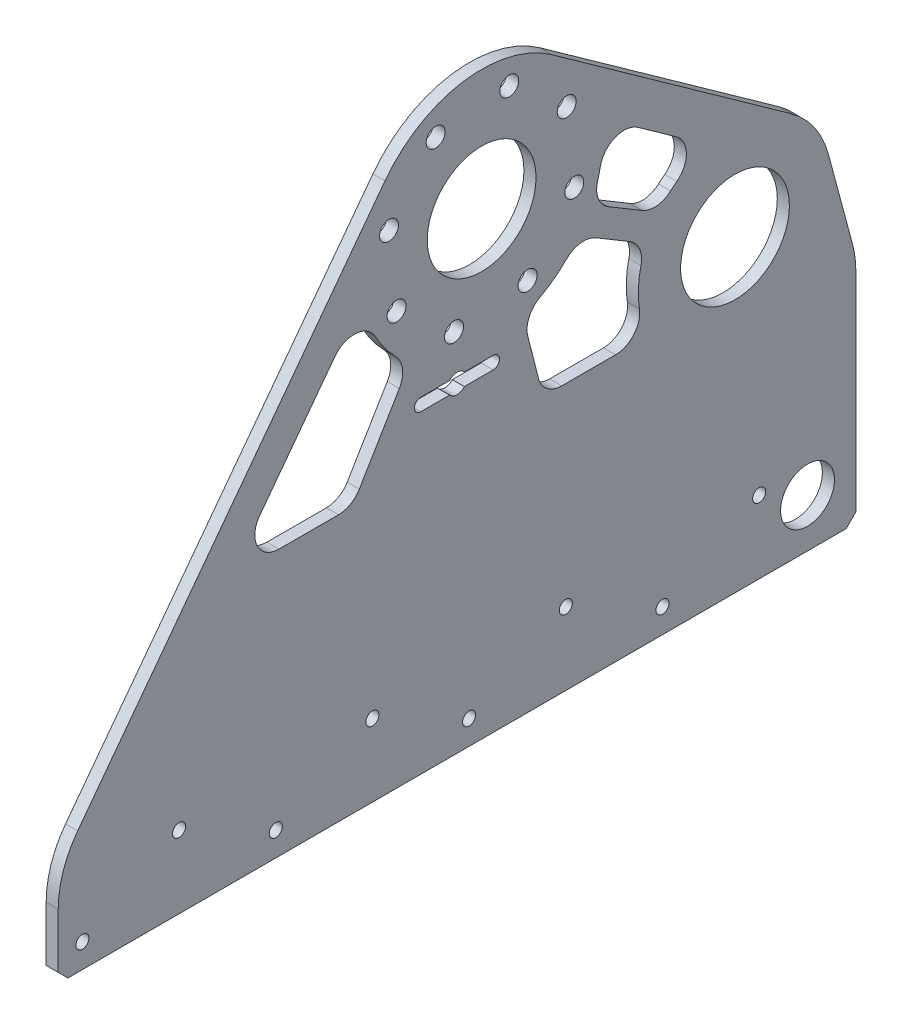
SolidWorks part; units mm, degrees
material "6061-T6 (SS)"
ref_plane "Front Plane" through (0, 0, 0) normal (0, 0, 1) x (1, 0, 0)
ref_plane "Top Plane" through (0, 0, 0) normal (0, 1, 0) x (1, 0, 0)
ref_plane "Right Plane" through (0, 0, 0) normal (1, 0, 0) x (0, 0, -1)
sketch "Sketch1" plane through (0, 0, 0) normal (1, 0, 0) x (0, 0, -1)
  line L0 (0, -25.4) -> (0, 31.864)
  line L13 (-209.55, -25.4) -> (0, -25.4)
  line L14 (-209.55, -25.4) -> (-209.55, -8.4756)
  line L15 (-204.4603, 6.7773) -> (-123.6994, 114.3161)
  line L16 (-209.55, 0) -> (0, 0) construction
  line L17 (-7.2155, 62.1365) -> (-0.8655, 38.438)
  line L18 (-79.8716, 121.0963) -> (-16.9981, 76.2396)
  circle A5 centre (-31.75, 55.5625) radius 14.2875
  circle A6 centre (-98.3115, 95.25) radius 14.2875 construction
  arc A7 (-79.8716, 121.0963) -> (-123.6994, 114.3161) centre (-98.3115, 95.25) ccw
  arc A8 (-16.9981, 76.2396) -> (-7.2155, 62.1365) centre (-31.75, 55.5625) cw
  circle A9 centre (-98.3115, 95.25) radius 14.2875
  arc A10 (-209.55, -8.4756) -> (-204.4603, 6.7773) centre (-184.15, -8.4756) cw
  arc A11 (-0.8655, 38.438) -> (0, 31.864) centre (-25.4, 31.864) cw
  point P4 (0, 0)
  dimension "D4" = 31.75
  dimension "D7" = 25.4
  dimension "D10" = 28.575
  dimension "D3" = 41.275
  dimension "D9" = 25.4
  dimension "D12" = 77.4954
  dimension "D13" = 63.5
  dimension "D14" = 63.5
  dimension "D5" = 25.4
  dimension "D8" = 28.575
  dimension "D2" = 15
  dimension "D6" = 209.55
extrude "Boss-Extrude1" add sketch "Sketch1" along normal blind 3.175
hole_wizard "#10 Clearance Hole1" positions "Sketch2" profile "Sketch3" hole size "#10" standard "ANSI Inch" end condition through all
sketch "Sketch2" plane through (3.175, 0, 0) normal (1, 0, 0) x (0, 0, -1)
  line L0 (-98.3115, 95.25) -> (-31.75, 55.5625) construction
  line L1 (-72.9115, 95.25) -> (-86.2351, 72.9046) construction
  circle A0 centre (-98.3115, 95.25) radius 25.4 construction
  circle A1 centre (-31.75, 55.5625) radius 14.2875 construction
  point P17 (-91.0503, 119.59)
  point P38 (-75.9661, 107.3265)
  point P39 (-73.9716, 87.9887)
  point P40 (-86.2351, 72.9046)
  point P41 (-105.5728, 70.91)
  point P42 (-120.657, 83.1735)
  point P43 (-122.6515, 102.5113)
  point P44 (-110.388, 117.5954)
  dimension "D1" = 50.8
  dimension "D2" = 8
sketch "Sketch3" plane through (3.175, 119.59, 91.0503) normal (0, 1, 0) x (0, 0, -1)
  line L0 (0, 0) -> (0, 3.175)
  line L1 (0, 3.175) -> (2.4892, 3.175)
  line L2 (2.4892, 3.175) -> (2.4892, 0)
  line L5 (2.4892, 0) -> (0, 0)
  line L11 (0, -6.35) -> (0, 107.95) construction
  dimension "Thru Hole Dia." = 4.9784
  dimension "Thru Hole Depth" = 3.175
sketch "Sketch9" plane through (3.175, 0, 0) normal (1, 0, 0) x (0, 0, -1)
  line L0 (0, 0) -> (-208.0942, 0) construction
  line L1 (0, -25.4) -> (0, 31.864) construction
  line L2 (0, -25.4) -> (0, 31.864) construction
  line L3 (-209.55, -25.4) -> (0, -25.4) construction
  line L4 (-164.2565, 44.45) -> (-129.699, 90.4657)
  line L5 (-123.6994, 114.3161) -> (-204.4603, 6.7773) construction
  line L6 (-176.1684, 44.45) -> (-132.2977, 44.45) construction
  line L7 (-164.2565, 44.45) -> (-132.2977, 44.45)
  line L8 (-66.9456, 100.1737) -> (-38.6711, 80.0014)
  line L9 (-16.9981, 76.2396) -> (-79.8716, 121.0963) construction
  line L10 (-69.5519, 81.7985) -> (-51.7692, 71.1955)
  line L11 (-55.0212, 65.7415) -> (-72.8039, 76.3444)
  line L12 (-98.3115, 95.25) -> (-31.75, 55.5625) construction
  line L13 (-98.3115, 95.25) -> (-132.7027, 37.5711) construction
  line L14 (-98.3115, 95.25) -> (-81.8784, 30.2801) construction
  line L15 (-117.2171, 69.7423) -> (-132.2977, 44.45)
  line L16 (-124.9046, 44.45) -> (-111.763, 66.4903) construction
  line L17 (-93.6431, 63.8451) -> (-88.7375, 44.45) construction
  line L18 (-82.1875, 44.45) -> (-87.487, 65.4022)
  line L19 (-82.1875, 44.45) -> (0, 44.45) construction
  line L20 (-82.1875, 44.45) -> (-54.5901, 44.45)
  line L21 (-124.9046, 44.45) -> (-88.7375, 44.45) construction
  line L22 (-124.9046, 44.45) -> (-88.7375, 44.45) construction
  circle A0 centre (-12.7, -12.7) radius 7.0739
  arc A2 (-204.4603, 6.7773) -> (-209.55, -8.4756) centre (-184.15, -8.4756) ccw construction
  arc A3 (-69.5519, 81.7985) -> (-117.2171, 69.7423) centre (-98.3115, 95.25) ccw construction
  arc A4 (-79.8716, 121.0963) -> (-123.6994, 114.3161) centre (-98.3115, 95.25) ccw construction
  arc A5 (-55.0212, 65.7415) -> (-51.7692, 71.1955) centre (-31.75, 55.5625) ccw construction
  arc A6 (-7.2155, 62.1365) -> (-16.9981, 76.2396) centre (-31.75, 55.5625) ccw construction
  arc A7 (-129.699, 90.4657) -> (-117.2171, 69.7423) centre (-98.3115, 95.25) ccw
  arc A8 (-54.5901, 44.45) -> (-55.0212, 65.7415) centre (-31.75, 55.5625) cw
  arc A9 (-51.7692, 71.1955) -> (-38.6711, 80.0014) centre (-31.75, 55.5625) cw
  arc A10 (-69.5519, 81.7985) -> (-66.9456, 100.1737) centre (-98.3115, 95.25) ccw
  arc A11 (-87.487, 65.4022) -> (-72.8039, 76.3444) centre (-98.3115, 95.25) ccw construction
  arc A12 (-87.487, 65.4022) -> (-72.8039, 76.3444) centre (-98.3115, 95.25) ccw
  arc A13 (-111.763, 66.4903) -> (-93.6431, 63.8451) centre (-98.3115, 95.25) ccw construction
  arc A14 (-111.763, 66.4903) -> (-93.6431, 63.8451) centre (-98.3115, 95.25) ccw construction
  dimension "D1" = 14.1478
  dimension "D3" = 12.7
  dimension "D2" = 12.7
  dimension "D4" = 9.525
  dimension "D5" = 44.45
  dimension "D6" = 9.525
  dimension "D7" = 6.35
  dimension "D8" = 6.35
  dimension "D9" = 6.35
  dimension "D10" = 45
  dimension "D11" = 45
extrude "Cut-Extrude1" cut sketch "Sketch9" against normal through all
fillet "Fillet1" radius 6.35 13 edges at (1.5875, 100.1737, 66.9456) (1.5875, 71.1955, 51.7692) (1.5875, 81.7985, 69.5519) (1.5875, 80.0014, 38.6711) (1.5875, 76.3444, 72.8039) (1.5875, 65.7415, 55.0212) (1.5875, 44.45, 82.1875) (1.5875, 65.4022, 87.487) (1.5875, 44.45, 54.5901) (1.5875, 44.45, 164.2565) (1.5875, 90.4657, 129.699) (1.5875, 69.7423, 117.2171) (1.5875, 44.45, 132.2977)
hole_wizard "1/8 (0.135) Diameter Hole1" positions "Sketch10" profile "Sketch11" hole size "1/8" standard "ANSI Inch" end condition through all
sketch "Sketch10" plane through (3.175, 0, 0) normal (1, 0, 0) x (0, 0, -1)
  point P4 (-177.8, -6.35)
  point P7 (-152.4, -19.05)
  point P10 (-127, -6.35)
  point P13 (-101.6, -19.05)
  point P16 (-76.2, -6.35)
  point P19 (-50.8, -19.05)
  point P22 (-25.4, -6.35)
  point P26 (-203.2, -19.05)
sketch "Sketch11" plane through (3.175, -6.35, 177.8) normal (0, 1, 0) x (0, 0, -1)
  line L0 (0, 0) -> (0, 3.175)
  line L1 (0, 3.175) -> (1.7145, 3.175)
  line L2 (1.7145, 3.175) -> (1.7145, 0)
  line L5 (1.7145, 0) -> (0, 0)
  line L11 (0, -6.35) -> (0, 107.95) construction
  dimension "Thru Hole Dia." = 3.429
  dimension "Thru Hole Depth" = 3.175
chamfer "Chamfer1" distance 2.54 angle 45 2 edges at (1.5875, -25.4, 0) (1.5875, -25.4, 209.55)
sketch "Sketch12" plane through (3.175, 0, 0) normal (1, 0, 0) x (0, 0, -1)
  line L5 (-102.8431, 60.3885) -> (-95.265, 60.3885)
  line L6 (-114.315, 58.7375) -> (-95.265, 58.7375) construction
  line L7 (-102.8431, 57.0865) -> (-95.265, 57.0865)
  line L8 (-114.315, 60.3885) -> (-106.7369, 60.3885)
  line L11 (-114.315, 57.0865) -> (-106.7369, 57.0865)
  line L12 (-95.265, 60.325) -> (-95.265, 57.15) construction
  line L13 (-341.2998, 60.325) -> (-114.315, 60.325) construction
  line L14 (-341.2998, 57.15) -> (-114.315, 57.15) construction
  line L15 (-114.315, 58.7375) -> (-123.7788, 58.7375) construction
  line L16 (-130.4505, 47.548) -> (-119.931, 65.1907) construction
  line L17 (-95.265, 58.7375) -> (-85.8013, 58.7375) construction
  line L18 (-86.1876, 60.2647) -> (-83.3998, 49.2429) construction
  arc A2 (-102.8431, 60.3885) -> (-106.7369, 60.3885) centre (-104.79, 58.7375) ccw
  arc A3 (-114.315, 60.3885) -> (-114.315, 57.0865) centre (-114.315, 58.7375) ccw
  arc A4 (-95.265, 57.0865) -> (-95.265, 60.3885) centre (-95.265, 58.7375) ccw
  arc A5 (-106.7369, 57.0865) -> (-102.8431, 57.0865) centre (-104.79, 58.7375) ccw
  point P3 (-104.79, 58.7375)
  point P29 (-91.2486, 60.3885)
  point P32 (0, 0)
  dimension "D3" = 5.1054
  dimension "D1" = 3.302
  dimension "D2" = 19.05
extrude "Cut-Extrude2" cut sketch "Sketch12" against normal through all
